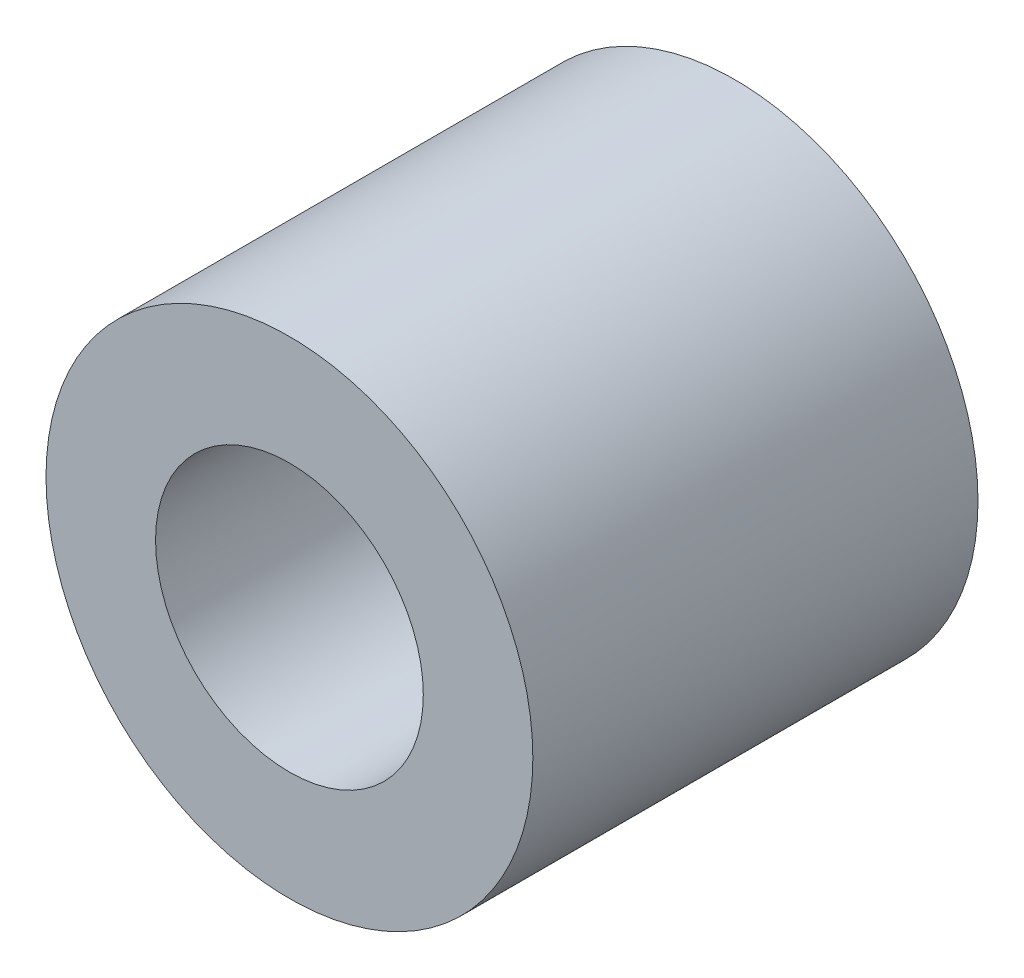
SolidWorks part; units mm, degrees
material "Nylon 101"
ref_plane "Front Plane" through (0, 0, 0) normal (0, 0, 1) x (1, 0, 0)
ref_plane "Top Plane" through (0, 0, 0) normal (0, 1, 0) x (1, 0, 0)
ref_plane "Right Plane" through (0, 0, 0) normal (1, 0, 0) x (0, 0, -1)
sketch "Sketch1" plane through (0, 0, 0) normal (0, 0, 1) x (1, 0, 0)
  circle A0 centre (0, 0) radius 9.525
  circle A1 centre (0, 0) radius 5.2387
  dimension "D1" = 19.05
  dimension "D2" = 10.4775
extrude "Boss-Extrude1" add sketch "Sketch1" along normal mid plane 17.4185
equation "\"D1@Boss-Extrude1\"=0.0625in+0.45mm/2"
